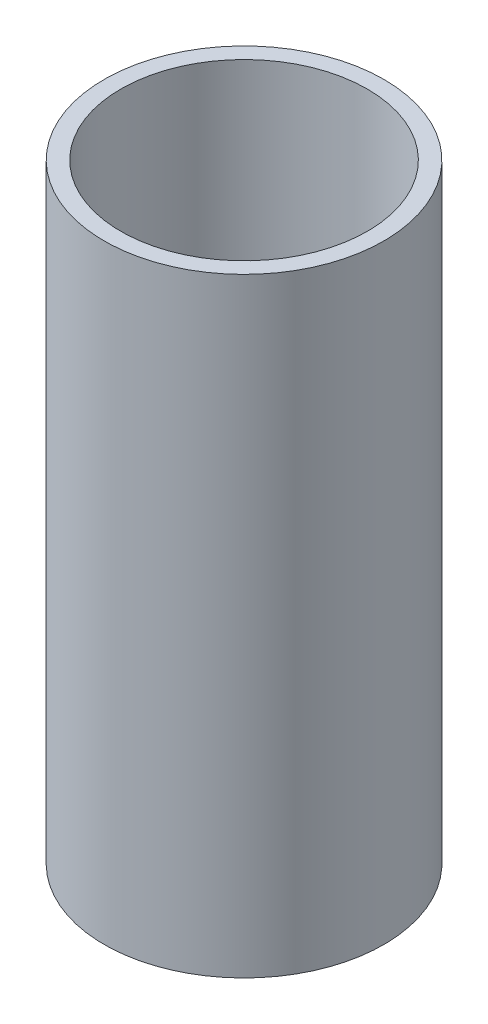
SolidWorks part; units mm, degrees
ref_plane "Front Plane" through (0, 0, 0) normal (0, 0, 1) x (1, 0, 0)
ref_plane "Top Plane" through (0, 0, 0) normal (0, 1, 0) x (1, 0, 0)
ref_plane "Right Plane" through (0, 0, 0) normal (1, 0, 0) x (0, 0, -1)
sketch "Sketch1" plane through (0, 0, 0) normal (0, 1, 0) x (1, 0, 0)
  circle A0 centre (0, 0) radius 40
  dimension "SLEEVE_OD" = 80
extrude "Boss-Extrude1" add sketch "Sketch1" along normal blind 174.2178
sketch "Sketch2" plane through (0, 0, 0) normal (0, 1, 0) x (1, 0, 0)
  circle A0 centre (0, 0) radius 35.2461
  dimension "BORE_D" = 70.4922
extrude "Cut-Extrude1" cut sketch "Sketch2" along normal through all
chamfer "Chamfer1" distance 3.8626 angle 45 rebuild error yes
